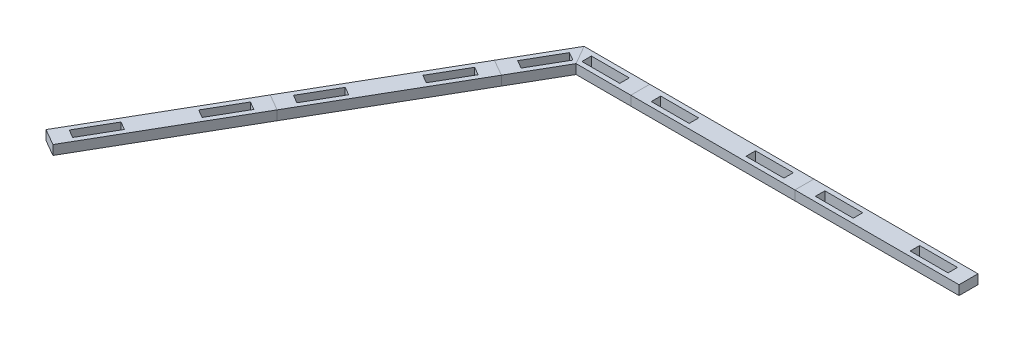
SolidWorks part; units mm, degrees
material "Cedar"
ref_plane "Front Plane" through (0, 0, 0) normal (0, 0, 1) x (1, 0, 0)
ref_plane "Top Plane" through (0, 0, 0) normal (0, 1, 0) x (1, 0, 0)
ref_plane "Right Plane" through (0, 0, 0) normal (1, 0, 0) x (0, 0, -1)
sketch "Sketch1" plane through (0, 0, 0) normal (0, 1, 0) x (1, 0, 0)
  line L0 (-54.9926, 0) -> (54.9926, 0) construction
  line L1 (-54.9926, 0) -> (0, -31.75)
  line L2 (0, -31.75) -> (54.9926, 0)
  line L3 (54.9926, 0) -> (54.9926, 63.5)
  line L4 (54.9926, 63.5) -> (0, 95.25)
  line L5 (0, 95.25) -> (-54.9926, 63.5)
  line L6 (-54.9926, 63.5) -> (-54.9926, 0)
  line L7 (0, -31.75) -> (0, 31.75) construction
  circle A0 centre (0, 31.75) radius 54.9926 construction
  point P9 (0, 0)
  dimension "D1" = 63.5
extrude "Boss-Extrude1" add sketch "Sketch1" against normal blind 6.35
sketch "Sketch2" plane through (0, 0, 0) normal (0, 1, 0) x (1, 0, 0)
  line L0 (-54.9926, 31.75) -> (54.9926, 31.75) construction
  line L1 (-54.9926, 63.5) -> (-54.9926, 0) construction
  line L2 (54.9926, 0) -> (54.9926, 63.5) construction
  point P2 (0, 31.75)
ref_axis "Axis1" through (0, 0, -31.75) along (0, 1, 0)
sketch "Sketch10" plane through (0, 0, 0) normal (0, 1, 0) x (1, 0, 0)
  line L0 (0, -31.75) -> (-16.4978, -22.225) construction
  line L1 (-16.4978, -22.225) -> (-7.8235, -19.9007)
  line L2 (-7.8235, -19.9007) -> (-24.3213, -10.3757)
  line L3 (-24.3213, -10.3757) -> (-27.4963, -15.875)
  line L4 (-16.4978, -22.225) -> (-27.4963, -15.875)
  line L5 (-54.9926, 0) -> (0, -31.75) construction
  dimension "D1" = 45
  dimension "D2" = 6.35
extrude "Cut-Extrude4" cut sketch "Sketch10" against normal through all
sketch "Sketch11" plane through (0, 0, 0) normal (0, 1, 0) x (1, 0, 0)
  line L0 (-27.4963, -15.875) -> (-54.9926, 0) construction
  line L1 (-27.4963, -15.875) -> (-30.6713, -21.3743)
  line L2 (-30.6713, -21.3743) -> (-47.1691, -11.8493)
  line L3 (-47.1691, -11.8493) -> (-38.4948, -9.525)
  line L4 (-38.4948, -9.525) -> (-27.4963, -15.875)
  line L5 (-38.4948, -9.525) -> (-54.9926, 0) construction
  line L6 (-38.4948, -9.525) -> (-54.9926, 0) construction
  line L7 (-54.9926, 0) -> (-27.4963, -15.875) construction
  line L8 (-54.9926, 63.5) -> (-54.9926, 0) construction
  dimension "D1" = 45
  dimension "D2" = 6.35
extrude "Boss-Extrude4" add sketch "Sketch11" against normal blind 6.35
pattern_circular "CirPattern1" count 2 every 60 about axis through (0, 0, -31.75) along (0, 1, 0) of "Cut-Extrude4", "Boss-Extrude4"
sketch "Sketch12" plane through (0, 0, 0) normal (0, 1, 0) x (1, 0, 0)
  line L0 (-54.9926, 12.7) -> (54.9926, 12.7)
  line L1 (-54.9926, 63.5) -> (-54.9926, 0) construction
  line L2 (54.9926, 0) -> (54.9926, 63.5) construction
  line L3 (54.9926, 12.7) -> (54.9926, 95.25)
  line L4 (54.9926, 95.25) -> (-54.9926, 95.25)
  line L5 (-54.9926, 95.25) -> (-54.9926, 12.7)
  line L6 (0, 0) -> (0, 12.7) construction
  dimension "D1" = 12.7
extrude "Cut-Extrude5" cut sketch "Sketch12" against normal through all
sketch "Sketch13" plane through (0, 0, 0) normal (0, 1, 0) x (1, 0, 0)
  line L0 (0, 0) -> (0, 12.7) construction
  line L1 (-54.9926, 12.7) -> (54.9926, 12.7) construction
  line L2 (-31.75, 6.35) -> (31.75, 6.35) construction
  line L4 (-44.45, 9.525) -> (-19.05, 9.525)
  line L5 (-44.45, 9.525) -> (-44.45, 3.175)
  line L6 (-44.45, 3.175) -> (-19.05, 3.175)
  line L7 (-19.05, 9.525) -> (-19.05, 3.175)
  line L8 (-44.45, 9.525) -> (-19.05, 3.175) construction
  line L9 (-44.45, 3.175) -> (-19.05, 9.525) construction
  line L10 (19.05, 9.525) -> (44.45, 9.525)
  line L11 (19.05, 9.525) -> (19.05, 3.175)
  line L12 (19.05, 3.175) -> (44.45, 3.175)
  line L13 (44.45, 9.525) -> (44.45, 3.175)
  line L14 (19.05, 9.525) -> (44.45, 3.175) construction
  line L15 (19.05, 3.175) -> (44.45, 9.525) construction
  point P7 (0, 6.35)
  point P8 (0, 6.35)
  dimension "D1" = 6.35
  dimension "D2" = 25.4
  dimension "D3" = 6.35
  dimension "D4" = 25.4
  dimension "D5" = 63.5
extrude "Cut-Extrude6" cut sketch "Sketch13" against normal through all
pattern_linear "LPattern1" count 5 spacing 109.9852 along (1, 0, 0) count 2 spacing 109.9852 along (-1, 0, 0) pattern seed only yes of bodies 136 131
sketch "Sketch14" plane through (0, 0, 0) normal (0, 1, 0) x (1, 0, 0)
  line L0 (439.9409, -31.75) -> (439.9409, 12.7)
  line L1 (384.9483, 12.7) -> (494.9335, 12.7) construction
  line L2 (439.9409, 12.7) -> (494.9335, 12.7)
  line L3 (494.9335, 12.7) -> (494.9335, -31.75)
  line L4 (494.9335, -31.75) -> (439.9409, -31.75)
  line L5 (-109.9852, -31.75) -> (-109.9852, 12.7)
  line L6 (-164.9778, 12.7) -> (-54.9926, 12.7) construction
  line L7 (-109.9852, 12.7) -> (-164.9778, 12.7)
  line L8 (-164.9778, 12.7) -> (-164.9778, -31.75)
  line L9 (-164.9778, -31.75) -> (-109.9852, -31.75)
  line L10 (415.6196, -10.3757) -> (428.9424, 12.7)
  line L11 (428.9424, 12.7) -> (439.9409, 12.7)
  line L12 (415.6196, -10.3757) -> (409.2696, -21.3743)
  line L13 (409.2696, -21.3743) -> (439.9409, -31.75)
  line L14 (-79.3139, -21.3743) -> (-98.9867, 12.7)
  line L15 (-98.9867, 12.7) -> (-109.9852, 12.7)
  line L16 (-79.3139, -21.3743) -> (-95.8117, -30.8993)
  line L17 (-95.8117, -30.8993) -> (-109.9852, -31.75)
  line L18 (-85.6639, -10.3757) -> (-79.3139, -21.3743) construction
  line M5 (484.3909, 9.525) -> (484.3909, 3.175)
  line M6 (484.3909, 3.175) -> (458.9909, 3.175)
  line M7 (458.9909, 3.175) -> (458.9909, 9.525)
  line M8 (458.9909, 9.525) -> (484.3909, 9.525)
  line M13 (494.9335, 12.7) -> (384.9483, 12.7)
  line M19 (415.6196, -10.3757) -> (432.1174, -19.9007)
  line M20 (432.1174, -19.9007) -> (423.4431, -22.225)
  line M21 (423.4431, -22.225) -> (439.9409, -31.75)
  line M22 (439.9409, -31.75) -> (456.4387, -22.225)
  line M23 (456.4387, -22.225) -> (454.1144, -30.8993)
  line M24 (454.1144, -30.8993) -> (470.6122, -21.3743)
  line M25 (470.6122, -21.3743) -> (464.2622, -10.3757)
  line M26 (464.2622, -10.3757) -> (480.76, -0.8507)
  line M27 (480.76, -0.8507) -> (478.4357, -9.525)
  line M28 (478.4357, -9.525) -> (494.9335, 0)
  line M29 (494.9335, 0) -> (494.9335, 12.7)
extrude "Cut-Extrude7" cut sketch "Sketch14" against normal through all contours L17 L16 L14 L15 L5 | L10 L0 M19 M20 M21 M13 | L0 M22 M23 M24 M25 M26 M27 M28 M29 M13 M8 M5 M6 M7 | L8 L9 L5 L7 region at (431.3731, 0, 7.3494) region at (460.5225, 0, 5.1278) region at (-137.4815, 0, 9.525) region at (-98.715, 0, 11.4335)
sketch "Sketch15" plane through (0, 0, 0) normal (0, 1, 0) x (1, 0, 0)
  line L0 (-222.3722, 0) -> (552.3278, 0)
  line L3 (-222.3722, 0) -> (-222.3722, -63.5)
  line L4 (-222.3722, -63.5) -> (552.3278, -63.5)
  line L5 (552.3278, -63.5) -> (552.3278, 0)
  line L6 (164.9778, 0) -> (164.9778, 12.7)
  line L7 (164.9778, 12.7) -> (552.3278, 12.7)
  line L8 (552.3278, 12.7) -> (552.3278, 0)
  point P4 (164.9778, 0)
  line M15 (-54.9926, 0) -> (-38.4948, -9.525)
  line M16 (-38.4948, -9.525) -> (-47.1691, -11.8493)
  line M17 (-47.1691, -11.8493) -> (-30.6713, -21.3743)
  line M18 (-30.6713, -21.3743) -> (-24.3213, -10.3757)
  line M19 (-24.3213, -10.3757) -> (-7.8235, -19.9007)
  line M20 (-7.8235, -19.9007) -> (-16.4978, -22.225)
  line M21 (-16.4978, -22.225) -> (0, -31.75)
  line M22 (0, -31.75) -> (16.4978, -22.225)
  line M23 (16.4978, -22.225) -> (14.1735, -30.8993)
  line M24 (14.1735, -30.8993) -> (30.6713, -21.3743)
  line M25 (30.6713, -21.3743) -> (24.3213, -10.3757)
  line M26 (24.3213, -10.3757) -> (40.8191, -0.8507)
  line M27 (40.8191, -0.8507) -> (38.4948, -9.525)
  line M28 (38.4948, -9.525) -> (54.9926, 0)
  dimension "D1" = 63.5
  dimension "D2" = 774.7
extrude "Cut-Extrude8" cut sketch "Sketch15" against normal through all contours L8 L7 L6 L0 | L4 L5 L0 L3 M28 M27 M26 M25 M24 M23 M22 M21 M20 M19 M18 M17 M16 M15 | L0 M15 M16 M17 M18 M19 M20 M21 M22 M23 M24 M25 M26 M27 M28 | L5 L0 L3 L4 region at (171.108, 0, 32.504) region at (-1.6087, 0, 11.2607) region at (358.6528, 0, -6.35)
mirror "Mirror1" about plane through (-68.7408, -6.35, 39.6875) normal (0.866, 0, -0.5) of bodies 151 149 146
